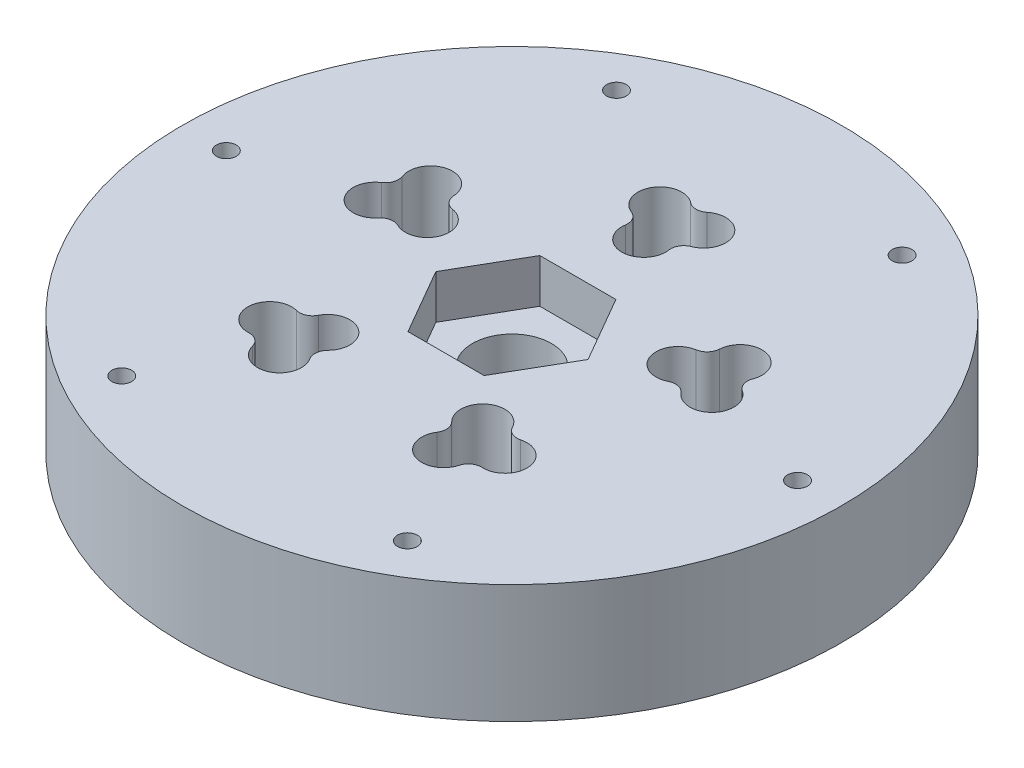
SolidWorks part; units mm, degrees
ref_plane "Front Plane" through (0, 0, 0) normal (0, 0, 1) x (1, 0, 0)
ref_plane "Top Plane" through (0, 0, 0) normal (0, 1, 0) x (1, 0, 0)
ref_plane "Right Plane" through (0, 0, 0) normal (1, 0, 0) x (0, 0, -1)
sketch "Sketch1" plane through (0, 0, 0) normal (0, 1, 0) x (1, 0, 0)
  circle A0 centre (0, 0) radius 75
  dimension "D1" = 150
extrude "Bloco" add sketch "Sketch1" against normal blind 27
sketch "Sketch2" plane through (0, 0, 0) normal (0, 1, 0) x (-1, 0, 0)
  line L0 (0, -75) -> (0, 75) construction
  line L1 (75, 0) -> (-75, 0) construction
  line L3 (-8.6603, 15) -> (-17.3205, 0)
  line L4 (-17.3205, 0) -> (-8.6603, -15)
  line L5 (-8.6603, -15) -> (8.6603, -15)
  line L6 (8.6603, -15) -> (17.3205, 0)
  line L7 (17.3205, 0) -> (8.6603, 15)
  line L8 (8.6603, 15) -> (-8.6603, 15)
  circle A0 centre (0, 0) radius 9
  circle A1 centre (0, 0) radius 75 construction
  circle A2 centre (0, 0) radius 15 construction
  point P10 (0, 15)
  dimension "D1" = 18
  dimension "D2" = 30
extrude "Furo Central - Ø18 Passante" cut sketch "Sketch2" against normal through all contours A0 region at (0, 0, 0)
extrude "Encaixe do Eixo" cut sketch "Sketch2<3>" against normal blind 10
sketch "Sketch2<3>" plane through (0, 0, 0) normal (0, 1, 0) x (-1, 0, 0) same geometry as "Sketch2"
sketch "Posição Furos de Fixação" plane through (0, -27, 0) normal (0, -1, 0) x (-1, 0, 0)
  line L0 (0, 0) -> (-65, 0) construction
  line L1 (0, 0) -> (-32.5, 56.2917) construction
  circle A0 centre (0, 0) radius 65 construction
  circle A1 centre (-32.5, 56.2917) radius 2
  circle A2 centre (32.5, 56.2917) radius 2
  circle A3 centre (65, 0) radius 2
  circle A4 centre (32.5, -56.2917) radius 2
  circle A5 centre (-32.5, -56.2917) radius 2
  circle A6 centre (-65, 0) radius 2
  point P6 (0, 0)
  point P19 (0, 0)
  dimension "D1" = 130
  dimension "D3" = 4
  dimension "D2" = 60
  dimension "D4" = 6
hole_wizard "Rebaixo - Furos de Fixação M4" positions "Sketch4" profile "Sketch5" counterbore size "M4" standard "ANSI Metric" end condition through all
sketch "Sketch4" plane through (0, -27, 0) normal (0, -1, 0) x (-1, 0, 0)
  point P0 (-32.5, 56.2917)
  point P3 (32.5, 56.2917)
  point P6 (65, 0)
  point P9 (32.5, -56.2917)
  point P12 (-32.5, -56.2917)
  point P15 (-65, 0)
sketch "Sketch5" plane through (32.5, -27, -56.2917) normal (1, 0, 0) x (0, 0, -1)
  line L0 (0, 0) -> (0, 27)
  line L1 (0, 27) -> (2.25, 27)
  line L3 (2.25, 27) -> (2.25, 4)
  line L4 (4, 4) -> (2.25, 4)
  line L5 (4, 4) -> (4, 0.025)
  line L6 (4, 0.025) -> (4.025, 0)
  line L7 (4.025, 0) -> (0, 0)
  line L8 (-4, 0.025) -> (-4.025, 0) construction
  line L11 (0, -6.35) -> (0, 107.95) construction
  dimension "Thru Hole Dia." = 4.5
  dimension "Thru Hole Depth" = 27
  dimension "C'Bore Dia." = 8
  dimension "C'Bore Depth" = 4
  dimension "Near C'Sink Dia." = 8.05
  dimension "Near C'Sink Angle" = 90
sketch "Sketch6" plane through (0, -27, 0) normal (0, -1, 0) x (-1, 0, 0)
  line L0 (0, 0) -> (0, 30) construction
  line L1 (-5, 38.6603) -> (5, 38.6603) construction
  arc A0 (-4.9427, 30.7548) -> (4.9427, 30.7548) centre (0, 30) ccw
  arc A1 (-1.875, 42.5634) -> (-6.8177, 34.0024) centre (-5, 38.6603) ccw
  arc A2 (6.8177, 34.0024) -> (1.875, 42.5634) centre (5, 38.6603) ccw
  arc A3 (-4.9427, 30.7548) -> (-6.8177, 34.0024) centre (-7.9083, 31.2076) ccw
  arc A4 (-1.875, 42.5634) -> (1.875, 42.5634) centre (0, 44.9053) ccw
  arc A5 (6.8177, 34.0024) -> (4.9427, 30.7548) centre (7.9083, 31.2076) ccw
  dimension "D2" = 10
  dimension "D4" = 6
  dimension "D1" = 30
  dimension "D3" = 10
extrude "Rasgo Dimensionado" cut sketch "Sketch6" against normal through all
pattern_circular "Rasgos" count 5 over 360 about axis through (0, -27, 0) along (0, 1, 0) of "Rasgo Dimensionado"
sketch "Sketch7" plane through (0, 0, 0) normal (1, 0, 0) x (0, 0, -1)
  line L0 (0, -27) -> (-53.5, -27)
  line L1 (-75, -27) -> (75, -27) construction
  line L2 (0, -27) -> (0, 0) construction
  circle A0 centre (-53.5, -27) radius 4
  dimension "D2" = 8
  dimension "D1" = 53.5
revolve "Canal - Raio de 4mm" cut sketch "Sketch7" angle 360 about L2 region at (0, -27, 57.3869)
